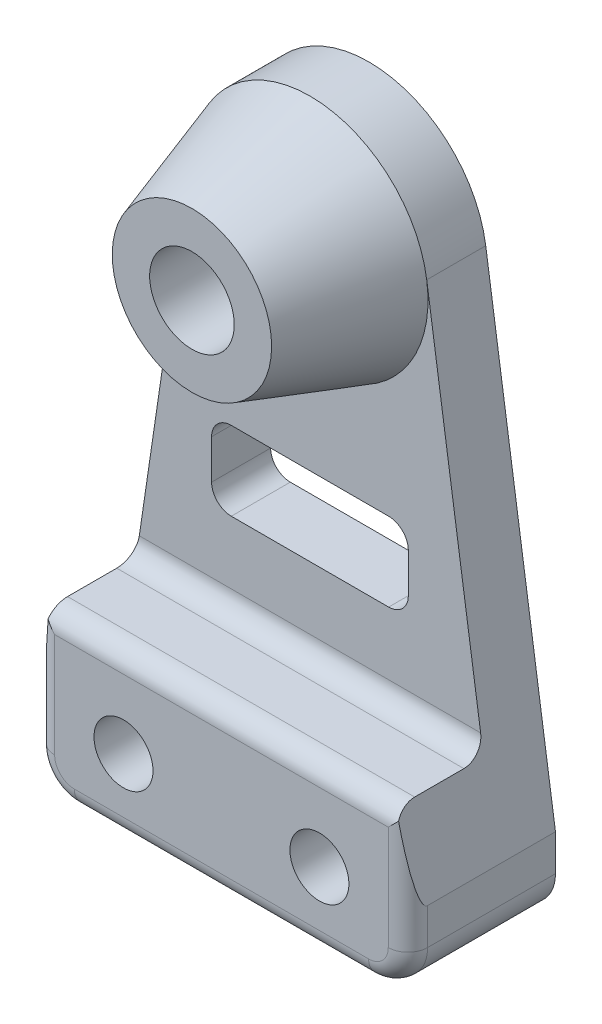
SolidWorks part; units mm, degrees
ref_plane "Спереди" through (0, 0, 0) normal (0, 0, 1) x (1, 0, 0)
ref_plane "Сверху" through (0, 0, 0) normal (0, 1, 0) x (1, 0, 0)
ref_plane "Справа" through (0, 0, 0) normal (1, 0, 0) x (0, 0, -1)
sketch "Sketch1" plane through (0, 0, 0) normal (0, 0, 1) x (1, 0, 0)
  line L0 (0, 0) -> (0, -38.4554) construction
  line L2 (-7.48, -27) -> (7.48, -27)
  line L3 (9.48, -23.15) -> (5.9358, 0.8756)
  line L4 (-5.9358, 0.8756) -> (-9.48, -23.15)
  line L5 (-9.48, -23.15) -> (-9.48, -25)
  line L6 (9.48, -23.15) -> (9.48, -25)
  circle A0 centre (0, 0) radius 2.15
  circle A1 centre (-4.98, -23.2) radius 1.5
  circle A2 centre (4.98, -23.2) radius 1.5
  arc A3 (5.9358, 0.8756) -> (-5.9358, 0.8756) centre (0, 0) ccw
  arc A6 (9.48, -25) -> (7.48, -27) centre (7.48, -25) cw
  arc A7 (-7.48, -27) -> (-9.48, -25) centre (-7.48, -25) cw
  dimension "D1" = 4.3
  dimension "D2" = 3
  dimension "D3" = 3
  dimension "D4" = 23.2
  dimension "D8" = 4.5
  dimension "D11" = 2
  dimension "D9" = 4.5
  dimension "D10" = 12
  dimension "D13" = 27
  dimension "D6" = 4.98
  dimension "D7" = 4.98
  dimension "D12" = 14.96
  dimension "D16" = 1.85
extrude "Extrude1" add sketch "Sketch1" along normal blind 3
sketch "Sketch2" plane through (0, 0, 3) normal (0, 0, 1) x (1, 0, 0)
  circle A0 centre (0, 0) radius 2.15
  circle A1 centre (0, 0) radius 6
  dimension "D1" = 4.3
  dimension "D2" = 12
extrude "Extrude2" add sketch "Sketch2" along normal blind 6
sketch "Sketch3" plane through (0, 0, 3) normal (0, 0, 1) x (1, 0, 0)
  line L0 (0, 1.2917) -> (0, -22.2917) construction
  line L1 (-4, -10.5) -> (4, -10.5)
  line L2 (-5, -11.5) -> (-5, -13.5)
  line L3 (-4, -14.5) -> (4, -14.5)
  line L4 (5, -11.5) -> (5, -13.5)
  arc A0 (-4, -10.5) -> (-5, -11.5) centre (-4, -11.5) ccw
  arc A1 (4, -10.5) -> (5, -11.5) centre (4, -11.5) cw
  arc A2 (4, -14.5) -> (5, -13.5) centre (4, -13.5) ccw
  arc A3 (-4, -14.5) -> (-5, -13.5) centre (-4, -13.5) cw
  point P8 (0, -10.5)
  point P12 (-5, -10.5)
  point P15 (5, -10.5)
  point P20 (-5, -14.5)
  dimension "D4" = 1
  dimension "D1" = 10.5
  dimension "D2" = 10
  dimension "D3" = 4
extrude "Extrude3" cut sketch "Sketch3" against normal up to surface (3 mm away) up to face at (0, -18.0316, 0)
sketch "Sketch4" plane through (0, 0, 3) normal (0, 0, 1) x (1, 0, 0)
  line L6 (-7.48, -27) -> (7.48, -27)
  line L7 (-9.48, -23.15) -> (-8.8235, -18.7)
  line L8 (-8.8235, -18.7) -> (8.8235, -18.7)
  line L9 (8.8235, -18.7) -> (9.48, -23.15)
  line L10 (9.48, -23.15) -> (9.48, -25)
  line L11 (-9.48, -23.15) -> (-9.48, -25)
  line L12 (-7.48, -27) -> (7.48, -27) construction
  line L13 (-9.48, -23.15) -> (-9.48, -25) construction
  line L15 (-5.9358, 0.8756) -> (-9.48, -23.15) construction
  line L16 (9.48, -23.15) -> (5.9358, 0.8756) construction
  line L17 (9.48, -25) -> (9.48, -23.15) construction
  circle A6 centre (-4.98, -23.2) radius 1.5
  circle A7 centre (4.98, -23.2) radius 1.5
  arc A8 (7.48, -27) -> (9.48, -25) centre (7.48, -25) ccw
  arc A9 (-9.48, -25) -> (-7.48, -27) centre (-7.48, -25) ccw
  dimension "D2" = 3
  dimension "D5" = 4.5
  dimension "D7" = 14.96
extrude "Extrude4" add sketch "Sketch4" along normal blind 4.5
fillet "Fillet5" radius 1 7 edges at (-9.48, -24.075, 7.5) (9.48, -24.075, 7.5) (0, -27, 7.5) (0, -18.7, 7.5) (0, -18.7, 3) (-8.8942, -26.4142, 7.5) (8.8942, -26.4142, 7.5)
chamfer "Chamfer1" distance 6 angle 18 1 edges at (6, 0, 9) first distance on face at (0, 0.4378, 1.5)
